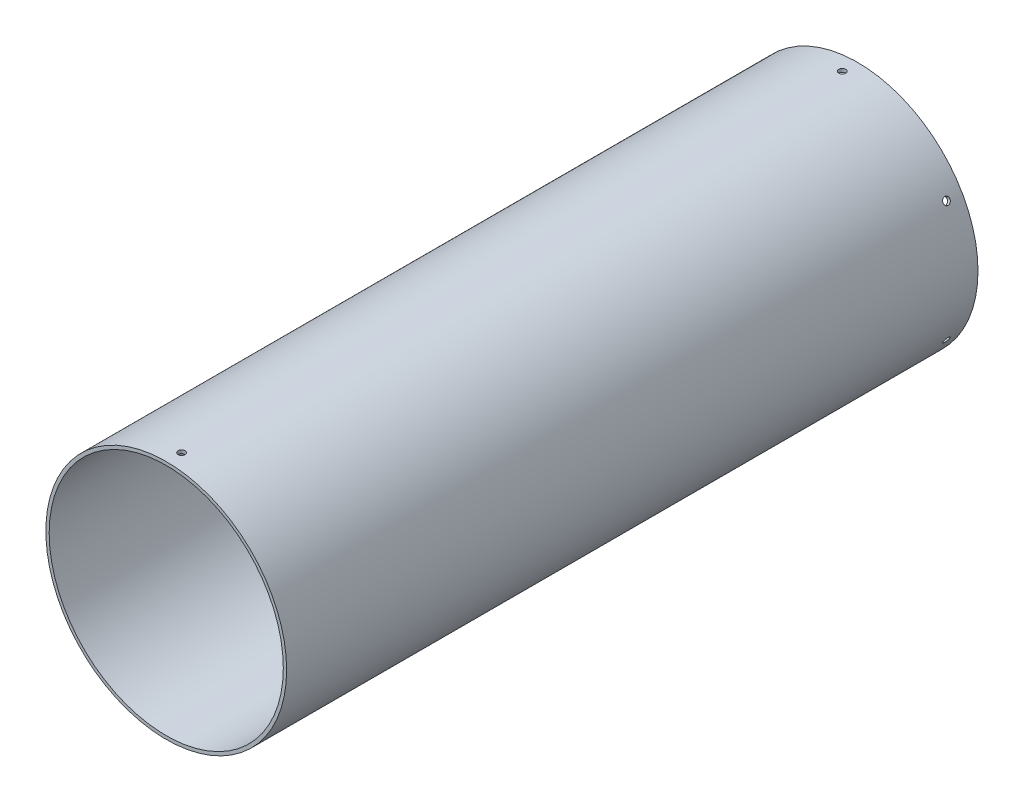
SolidWorks part; units mm, degrees
material "A-Glass Fiber"
ref_plane "Front Plane" through (0, 0, 0) normal (0, 0, 1) x (1, 0, 0)
ref_plane "Top Plane" through (0, 0, 0) normal (0, 1, 0) x (1, 0, 0)
ref_plane "Right Plane" through (0, 0, 0) normal (1, 0, 0) x (0, 0, -1)
sketch "Sketch1" plane through (0, 0, 0) normal (0, 0, 1) x (1, 0, 0)
  circle A0 centre (0, 0) radius 76.2
  circle A1 centre (0, 0) radius 78.359
  dimension "D1" = 156.718
  dimension "D2" = 152.4
extrude "Boss-Extrude1" add sketch "Sketch1" along normal blind 450
sketch "Sketch4" plane through (0, 0, 0) normal (0, 1, 0) x (1, 0, 0)
  line L0 (78.359, 0) -> (-78.359, 0) construction
  point P0 (0, -10)
  dimension "D1" = 10
hole_wizard "M4 Clearance Hole2" positions "Sketch4" profile "Sketch5" hole size "M4" standard "ANSI Metric" end condition through all
sketch "Sketch5" plane through (0, 0, 10) normal (1, 0, 0) x (0, 0, 1)
  line L0 (0, 0) -> (0, 78.359)
  line L1 (0, 78.359) -> (2.25, 78.359)
  line L2 (2.25, 78.359) -> (2.25, 0)
  line L5 (2.25, 0) -> (0, 0)
  line L11 (0, -6.35) -> (0, 107.95) construction
  dimension "Thru Hole Dia." = 4.5
  dimension "Thru Hole Depth" = 78.359
pattern_circular "CirPattern1" count 6 over 360 about axis through (0, 0, 450) along (0, 0, -1) of "M4 Clearance Hole2" reverse direction yes
sketch "Sketch6" plane through (0, 0, 0) normal (0, 1, 0) x (1, 0, 0)
  line L0 (-78.359, -450) -> (78.359, -450) construction
  point P0 (0, -440)
  dimension "D1" = 10
hole_wizard "M4 Clearance Hole3" positions "Sketch6" profile "Sketch7" hole size "M4" standard "ANSI Metric" end condition through all
sketch "Sketch7" plane through (0, 0, 440) normal (1, 0, 0) x (0, 0, -1)
  line L0 (0, 0) -> (0, 78.359)
  line L1 (0, 78.359) -> (2.25, 78.359)
  line L2 (2.25, 78.359) -> (2.25, 0)
  line L5 (2.25, 0) -> (0, 0)
  line L11 (0, -6.35) -> (0, 107.95) construction
  dimension "Thru Hole Dia." = 4.5
  dimension "Thru Hole Depth" = 78.359
